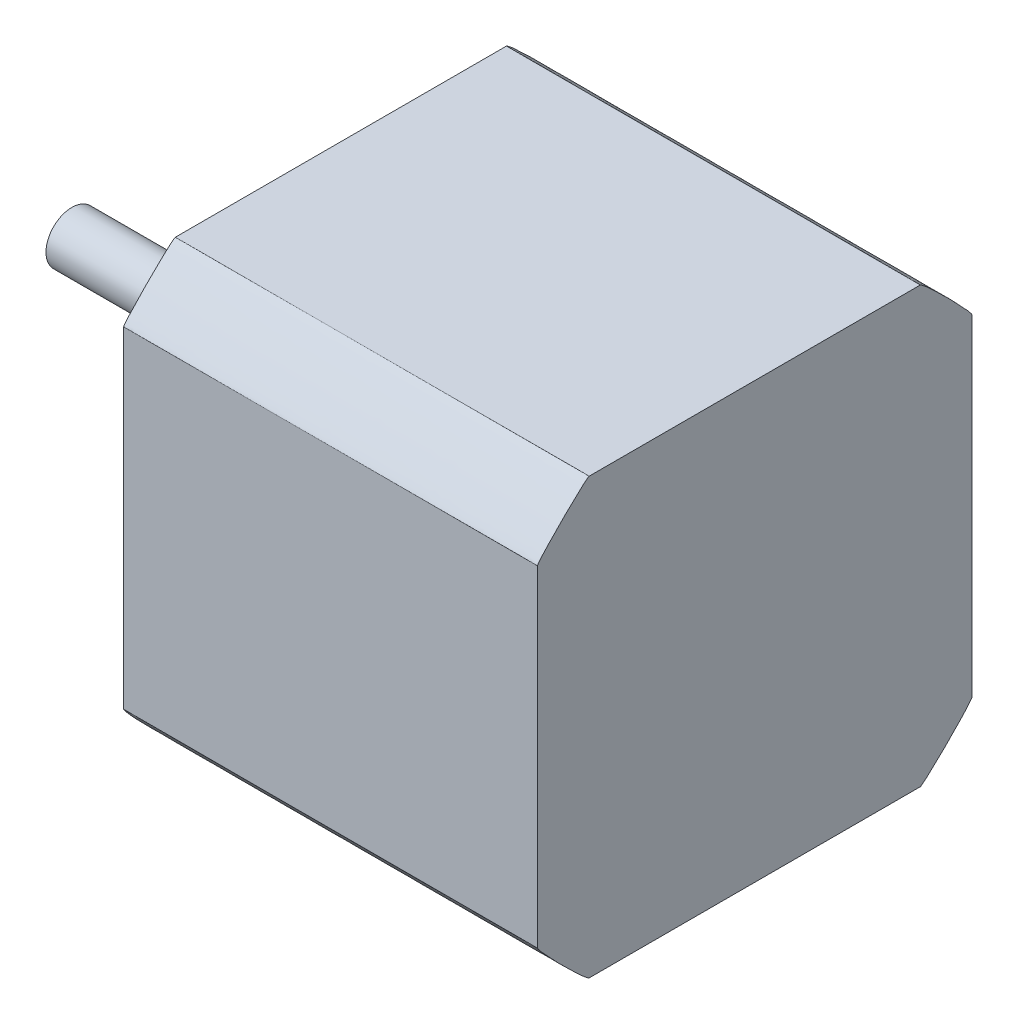
SolidWorks part; units mm, degrees
ref_plane "Front Plane" through (0, 0, 0) normal (0, 0, 1) x (1, 0, 0)
ref_plane "Top Plane" through (0, 0, 0) normal (0, 1, 0) x (1, 0, 0)
ref_plane "Right Plane" through (0, 0, 0) normal (1, 0, 0) x (0, 0, -1)
sketch "Sketch1" plane through (0, 0, 0) normal (1, 0, 0) x (0, 0, -1)
  line L1 (0, 0) -> (42, 0)
  line L2 (0, 0) -> (0, -42)
  line L3 (0, -42) -> (42, -42)
  line L4 (42, 0) -> (42, -42)
  dimension "D1" = 42
  dimension "D2" = 42
extrude "Boss-Extrude1" add sketch "Sketch1" along normal blind 40
sketch "Sketch2" plane through (0, 0, 0) normal (-1, 0, 0) x (0, 0, 1)
  circle A0 centre (-21, -21) radius 11
  dimension "D1" = 22
extrude "Boss-Extrude2" add sketch "Sketch2" along normal blind 2
sketch "Sketch3" plane through (-2, 0, 0) normal (-1, 0, 0) x (0, 0, 1)
  circle A0 centre (-21, -21) radius 2.5
  dimension "D1" = 5
extrude "Boss-Extrude3" add sketch "Sketch3" along normal blind 24
sketch "Sketch4" plane through (0, 0, 0) normal (-1, 0, 0) x (0, 0, 1)
  line L0 (-42, 0) -> (0, 0) construction
  line L1 (-42, -42) -> (-42, 0) construction
  circle A0 centre (-36.5, -5.5) radius 1.5
  circle A1 centre (-5.5, -5.5) radius 1.5
  circle A2 centre (-5.5, -36.5) radius 1.5
  circle A3 centre (-36.5, -36.5) radius 1.5
  dimension "D1" = 3
  dimension "D3" = 5.5
  dimension "D4" = 5.5
extrude "Cut-Extrude1" cut sketch "Sketch4" against normal blind 4.5
fillet "Fillet1" radius 5 4 edges at (20, -42, 0) (20, -42, -42) (20, 0, -42) (20, 0, 0) conic rho 0.05
equation "\"D3@Sketch4\"=(\"D1@Sketch1\"-31)/2"
equation "\"D4@Sketch4\"=\"D3@Sketch4\""
